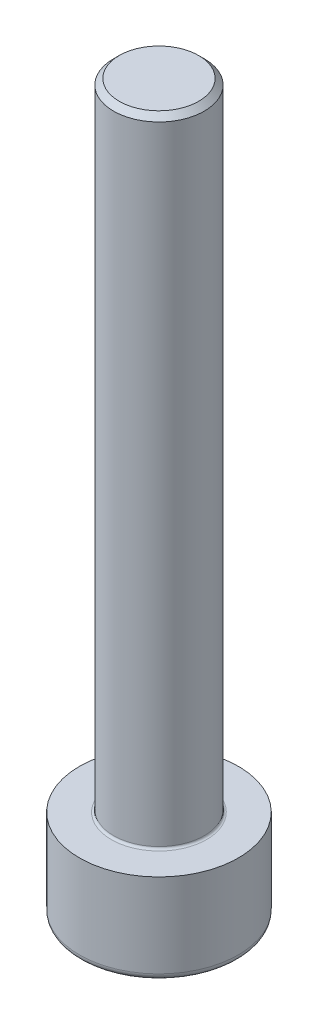
SolidWorks part; units mm, degrees
material "AISI 304"
ref_plane "前视基准面" through (0, 0, 0) normal (0, 0, 1) x (1, 0, 0)
ref_plane "上视基准面" through (0, 0, 0) normal (0, 1, 0) x (1, 0, 0)
ref_plane "右视基准面" through (0, 0, 0) normal (1, 0, 0) x (0, 0, -1)
other "Configuration Table"
sketch "草图1" plane through (0, 0, 0) normal (0, 0, 1) x (1, 0, 0)
  line L0 (0, 3.366) -> (0, 32)
  line L1 (0, 32) -> (1.75, 32)
  line L2 (1.75, 32) -> (2, 31.75)
  line L3 (2, 31.75) -> (2, 4.1)
  line L4 (2.1, 4) -> (3.5, 4)
  line L5 (3.5, 4) -> (3.5, 0.3)
  line L6 (3.2, 0) -> (1.5, 0)
  line L7 (1.5, 0) -> (1.5, 2.5)
  line L8 (1.5, 2.5) -> (0, 3.366)
  line L9 (0, 3.366) -> (0, 0) construction
  arc A0 (2, 4.1) -> (2.1, 4) centre (2.1, 4.1) ccw
  arc A1 (3.5, 0.3) -> (3.2, 0) centre (3.2, 0.3) cw
  dimension "D3" = 3
  dimension "r" = 0.1
  dimension "r2" = 0.3
  dimension "D1" = 1.5
  dimension "dk" = 7
  dimension "D2" = 120
  dimension "d" = 4
  dimension "k" = 4
  dimension "l" = 28
  dimension "内径" = 3.5
  dimension "D5" = 45
revolve "旋转1" add sketch "草图1" angle 360 about L9
sketch "草图2" plane through (0, 0, 0) normal (0, -1, 0) x (1, 0, 0)
  line L1 (1.5, -0.866) -> (1.5, 0.866)
  line L2 (1.5, 0.866) -> (0, 1.7321)
  line L3 (0, 1.7321) -> (-1.5, 0.866)
  line L4 (-1.5, 0.866) -> (-1.5, -0.866)
  line L5 (-1.5, -0.866) -> (0, -1.7321)
  line L6 (0, -1.7321) -> (1.5, -0.866)
  circle A0 centre (0, 0) radius 1.5 construction
  circle A1 centre (0, 0) radius 1.5 construction
extrude "切除-拉伸1" cut sketch "草图2" against normal up to surface (2.366 mm away) up to face at (-1.5, 2.5, 0)
